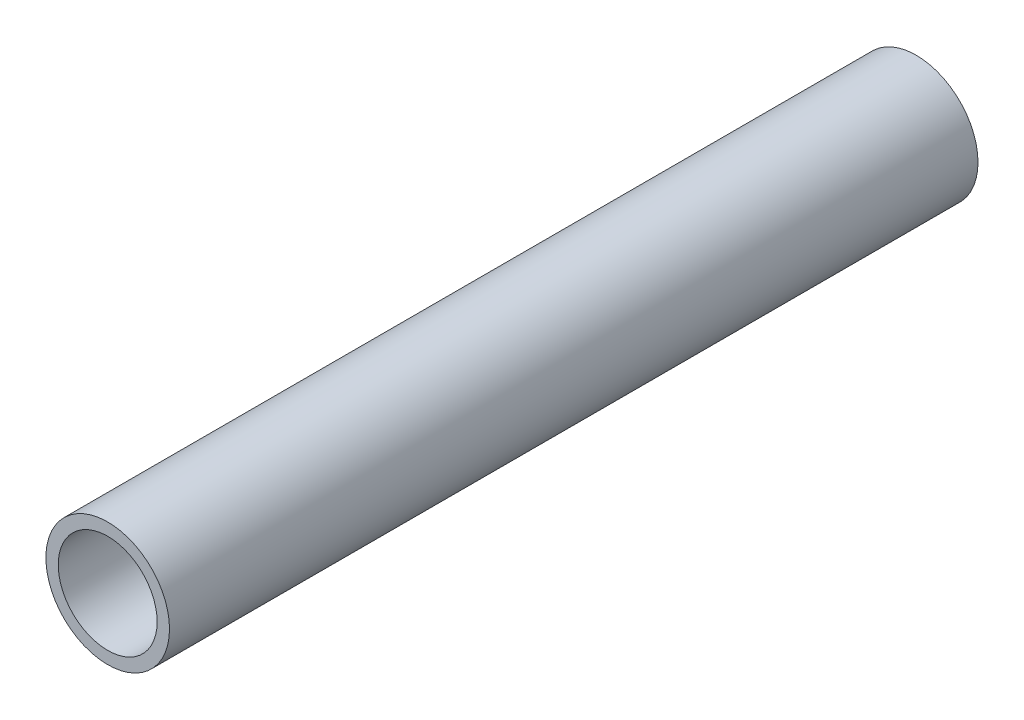
SolidWorks part; units mm, degrees
ref_plane "Front Plane" through (0, 0, 0) normal (0, 0, 1) x (1, 0, 0)
ref_plane "Top Plane" through (0, 0, 0) normal (0, 1, 0) x (1, 0, 0)
ref_plane "Right Plane" through (0, 0, 0) normal (1, 0, 0) x (0, 0, -1)
sketch "Sketch1" plane through (0, 0, 0) normal (0, 0, 1) x (1, 0, 0)
  circle A2 centre (0, 0) radius 10
  circle A3 centre (0, 0) radius 12.5
  dimension "D1" = 25
  dimension "D2" = 20
extrude "Boss-Extrude1" add sketch "Sketch1" against normal blind 145.5 and the other way blind 18
